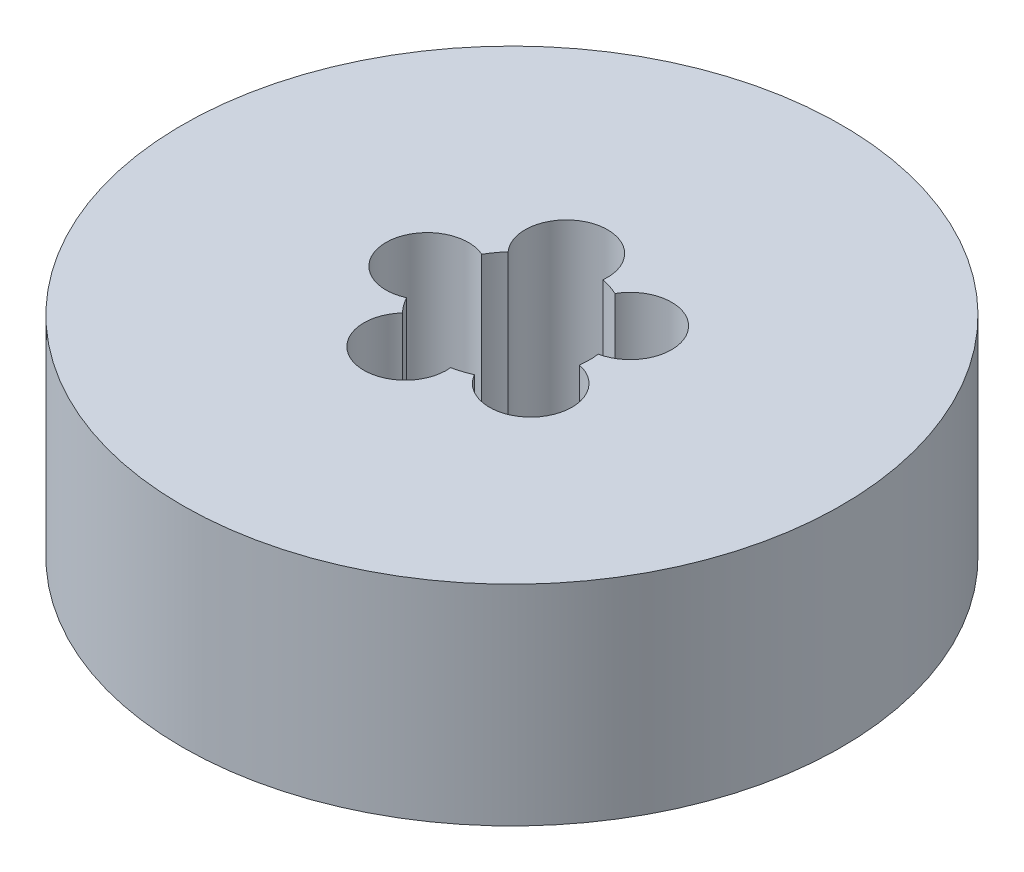
SolidWorks part; units mm, degrees
ref_plane "Front Plane" through (0, 0, 0) normal (0, 0, 1) x (1, 0, 0)
ref_plane "Top Plane" through (0, 0, 0) normal (0, 1, 0) x (1, 0, 0)
ref_plane "Right Plane" through (0, 0, 0) normal (1, 0, 0) x (0, 0, -1)
sketch "Sketch1" plane through (0, 0, 0) normal (0, 1, 0) x (1, 0, 0)
  circle A0 centre (0, 0) radius 42.5
  dimension "FLANGE_OD" = 85
extrude "Boss-Extrude1" add sketch "Sketch1" along normal blind 27
sketch "Sketch2" plane through (0, 0, 0) normal (0, 1, 0) x (1, 0, 0)
  circle A0 centre (0, 0) radius 10
  dimension "BORE_D" = 20
extrude "Cut-Extrude1" cut sketch "Sketch2" along normal through all
sketch "Sketch3" plane through (0, 27, 0) normal (0, 1, 0) x (1, 0, 0)
  circle A0 centre (0, 0) radius 10.9258 construction
  circle A1 centre (-10.9258, 0) radius 5.3195
  dimension "BOLT_D" = 10.6391
  dimension "BOLT_PCD" = 21.8515
extrude "Cut-Extrude2" cut sketch "Sketch3" against normal blind 24.1573
pattern_circular "CirPattern1" count 5 over 360 about axis through (0, 0, 0) along (0, 1, 0) of "Cut-Extrude2"
